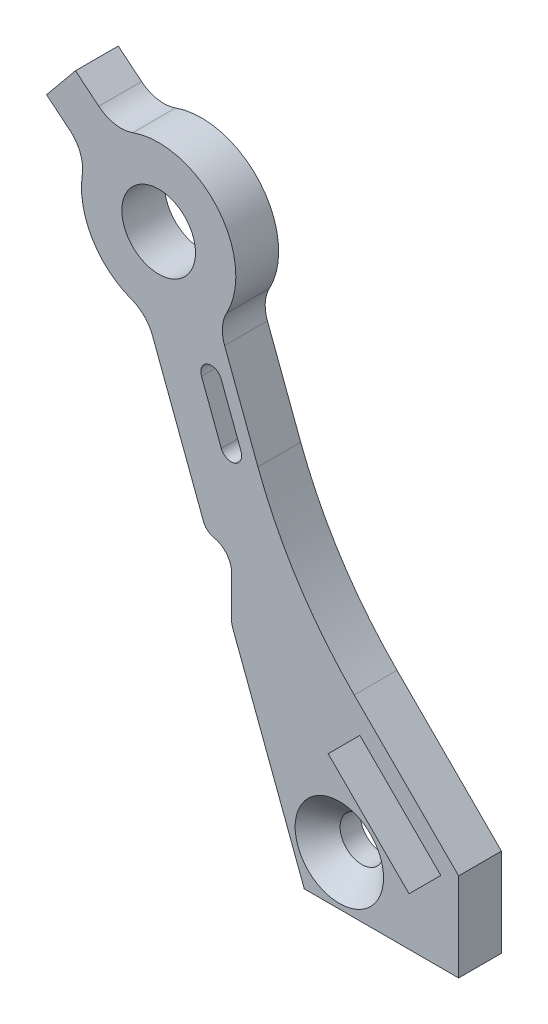
SolidWorks part; units mm, degrees
ref_plane "Front Plane" through (0, 0, 0) normal (0, 0, 1) x (1, 0, 0)
ref_plane "Top Plane" through (0, 0, 0) normal (0, 1, 0) x (1, 0, 0)
ref_plane "Right Plane" through (0, 0, 0) normal (1, 0, 0) x (0, 0, -1)
sketch "Sketch1" plane through (0, 0, 0) normal (0, 0, 1) x (1, 0, 0)
  line L0 (0, 11) -> (11, 0) construction
  line L1 (0, 0) -> (11, 0)
  line L2 (0, 0) -> (0, 11) construction
  line L3 (0, 11) -> (11, 11) construction
  line L4 (11, 0) -> (11, 11) construction
  line L5 (0, 0) -> (2.5, 0)
  line L6 (0, 0) -> (0, 3.5)
  line L7 (0, 3.5) -> (2.5, 3.5) construction
  line L8 (2.5, 0) -> (2.5, 3.5) construction
  line L9 (10.8939, 0) -> (10.947, 0.053) construction
  line L10 (7.4645, 3.4295) -> (1.7015, 9.1924)
  line L11 (1.7015, 9.1924) -> (3.9643, 11.4551)
  line L12 (7.4645, 3.4295) -> (9.7272, 5.6922)
  line L13 (3.9643, 11.4551) -> (9.7272, 5.6922)
  line L14 (0, 0) -> (-12.9496, 34.4032)
  line L15 (-12.9496, 34.4032) -> (-7.8021, 36.3407)
  line L16 (-7.8021, 36.3407) -> (-1.0208, 18.3247)
  line L17 (-1.0208, 18.3247) -> (11, 6.3039)
  line L18 (11, 0) -> (7.5175, 3.4825)
  line L19 (11, 6.3039) -> (11, 0)
  line L20 (0, 0) -> (0, 40.9886) construction
  line L21 (-10.3759, 35.372) -> (-17.3331, 41.0813) construction
  line L22 (-18.364, 39.8251) -> (-16.3023, 42.3375)
  line L23 (-16.3023, 42.3375) -> (-13.4069, 39.9614) construction
  line L24 (-18.364, 39.8251) -> (-15.4686, 37.4491)
  line L25 (-16.3023, 42.3375) -> (-13.4069, 39.9614)
  line L27 (-7.5879, 28.6748) -> (-5.6504, 23.5274)
  line L28 (-5.6504, 23.5274) -> (-4.2465, 24.0558)
  line L29 (-4.2465, 24.0558) -> (-6.184, 29.2032)
  line L30 (-6.184, 29.2032) -> (-7.5879, 28.6748)
  line L31 (-9.4268, 25.0442) -> (-6.6191, 26.1011) construction
  line L32 (-6.9609, 18.493) -> (-5.1729, 18.493)
  line L33 (-5.1729, 18.493) -> (-5.1729, 13.743)
  circle A0 centre (2.5, 3.5) radius 1.5
  circle A1 centre (-10.3759, 35.372) radius 2.625
  circle A3 centre (-10.3759, 35.372) radius 5.5
  point P28 (-17.3331, 41.0813)
  dimension "D5" = 3
  dimension "D6" = 5.25
  dimension "D7" = 11
  dimension "D1" = 11
  dimension "D2" = 11
  dimension "D3" = 3.5
  dimension "D4" = 2.5
  dimension "D8" = 45
  dimension "D9" = 6.3039
  dimension "D10" = 90
  dimension "D11" = 90
  dimension "D12" = 19.25
  dimension "D13" = 17
  dimension "D14" = 3.2
  dimension "D15" = 8.15
  dimension "D16" = 0.075
  dimension "D17" = 4.925
  dimension "D18" = 5.5
  dimension "D19" = 90
  dimension "D20" = 3.25
  dimension "D21" = 90
  dimension "D22" = 90
  dimension "D23" = 9
  dimension "D24" = 150
  dimension "D25" = 10
  dimension "D32" = 5.5
  dimension "D33" = 1.5
  dimension "D34" = 3
  dimension "D35" = 17
  dimension "D36" = 4.75
extrude "Boss-Extrude1" add sketch "Sketch1" along normal blind 3.05 contours A3 L14 L15 A1 L16 | L14 A3 L16 L15 A1 | A3 L14 L1 L12 L10 L11 L13 L19 L17 L16 A0 | L25 L22 L24 A3 | L24 A3 | A3 L14 region at (-0.3426, 12.9046, 0) region at (-15.0407, 32.7628, 0) region at (-9.1274, 32.0551, 0) region at (-15.9484, 39.945, 0)
hole_wizard "CSK for M3 Flat Head Machine Screw1" positions "Sketch2" profile "Sketch3" countersink size "M3" standard "ANSI Metric" end condition through all
sketch "Sketch2" plane through (0, 0, 3.05) normal (0, 0, 1) x (1, 0, 0)
  point P0 (2.5, 3.5)
sketch "Sketch3" plane through (2.5, 3.5, 3.05) normal (1, 0, 0) x (0, -1, 0)
  line L0 (0, 0) -> (0, 3.05)
  line L1 (0, 3.05) -> (1.55, 3.05)
  line L2 (1.55, 3.05) -> (1.55, 1.6)
  line L3 (1.55, 1.6) -> (3.15, 0)
  line L5 (3.15, 0) -> (0, 0)
  line L6 (-1.55, 1.6) -> (-3.15, 0) construction
  line L11 (0, -6.35) -> (0, 107.95) construction
  dimension "Thru Hole Dia." = 3.1
  dimension "Thru Hole Depth" = 3.05
  dimension "Near C'Sink Dia." = 6.3
  dimension "Near C'Sink Angle" = 90
fillet "Fillet2" radius 1.6 1 edges at (-5.1729, 18.493, 1.525)
fillet "Fillet3" radius 2.5 4 edges at (-13.4069, 39.9614, 1.525) (-15.4686, 37.4491, 1.525) (-11.2716, 29.9454, 1.525) (-6.1242, 31.8829, 1.525)
fillet "Fillet4" radius 30 1 edges at (-1.0208, 18.3247, 1.525)
fillet "Fillet5" radius 1 2 edges at (-6.9609, 18.493, 1.525) (-5.1729, 13.743, 1.525)
fillet "Fillet6" radius 0.75 4 edges at (-4.2465, 24.0558, 1.525) (-5.6504, 23.5274, 1.525) (-6.184, 29.2032, 1.525) (-7.5879, 28.6748, 1.525)
